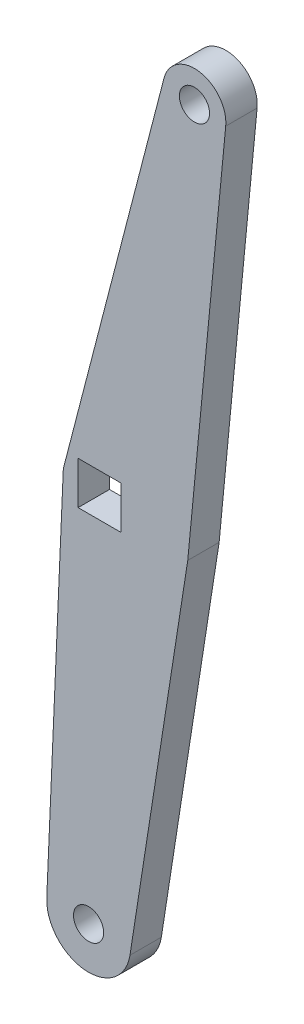
SolidWorks part; units mm, degrees
ref_plane "Front Plane" through (0, 0, 0) normal (0, 0, 1) x (1, 0, 0)
ref_plane "Top Plane" through (0, 0, 0) normal (0, 1, 0) x (1, 0, 0)
ref_plane "Right Plane" through (0, 0, 0) normal (1, 0, 0) x (0, 0, -1)
sketch "Sketch1" plane through (0, 0, 0) normal (0, 0, 1) x (1, 0, 0)
  line L0 (-6.344, 0.2767) -> (-3.8316, 57.887)
  line L1 (0, 0) -> (29.7258, 0) construction
  line L2 (6.2743, -0.9776) -> (15.0374, 55.2672)
  line L3 (-3.8316, 57.887) -> (11.4448, 116.8289)
  line L4 (15.0374, 55.2672) -> (20.7957, 115.1784)
  line L7 (5.0645, 93.8977) -> (16.088, 51.1976) construction
  line L8 (-3.8316, 57.887) -> (15.0374, 55.2672) construction
  line L9 (0, 0) -> (16.055, 115.6341) construction
  line L10 (-1.5908, 53.8877) -> (4.8862, 53.8877)
  line L11 (-1.5908, 53.8877) -> (-1.5908, 60.3647)
  line L12 (-1.5908, 60.3647) -> (4.8862, 60.3647)
  line L13 (4.8862, 53.8877) -> (4.8862, 60.3647)
  line L14 (-1.5908, 53.8877) -> (4.8862, 60.3647) construction
  line L15 (-1.5908, 60.3647) -> (4.8862, 53.8877) construction
  circle A0 centre (0, 0) radius 2.286
  arc A1 (-6.344, 0.2767) -> (6.2743, -0.9776) centre (0, 0) ccw
  circle A2 centre (16.055, 115.6341) radius 2.286
  arc A4 (20.7957, 115.1784) -> (11.4448, 116.8289) centre (16.055, 115.6341) ccw
  arc A10 (1.9601, 55.9159) -> (1.3352, 58.3366) centre (1.6477, 57.1262) ccw construction
  circle A11 centre (16.055, 115.6341) radius 1.905 construction
  point P2 (-3.9982, 57.9101)
  point P8 (1.6477, 57.1262)
  dimension "D1" = 12.7
  dimension "D2" = 4.572
  dimension "D5" = 6.477
  dimension "D8" = 9.525
  dimension "D3" = 19.05
  dimension "D11" = 6.477
extrude "Boss-Extrude1" add sketch "Sketch1" along normal blind 4.7625
